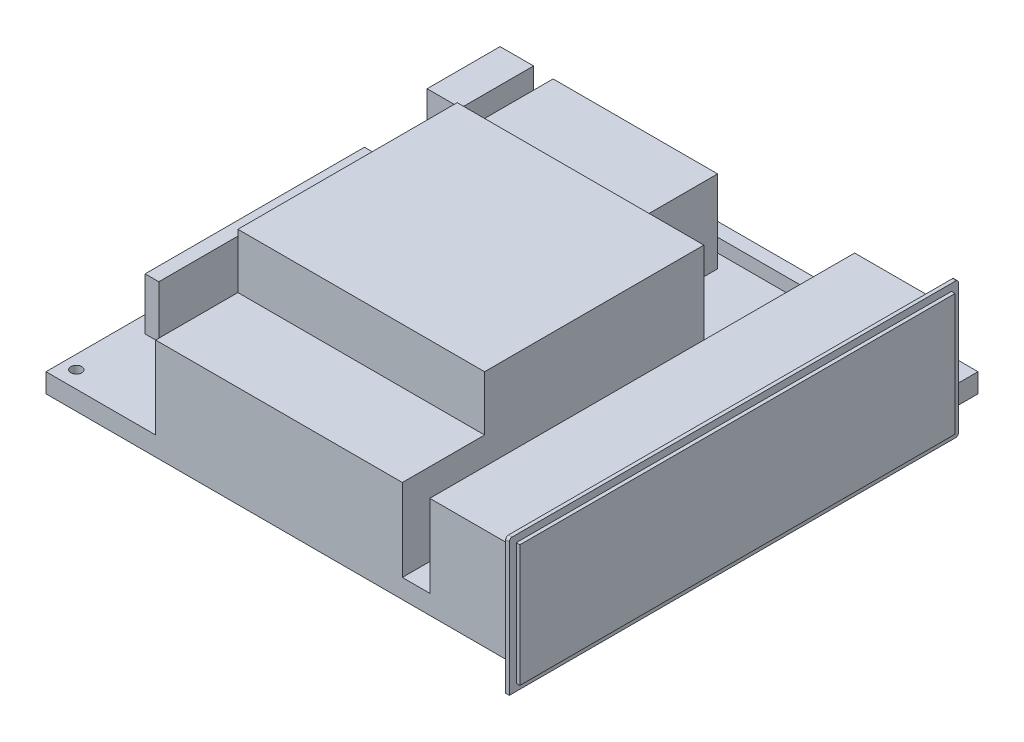
SolidWorks part; units mm, degrees
ref_plane "Front Plane" through (0, 0, 0) normal (0, 0, 1) x (1, 0, 0)
ref_plane "Top Plane" through (0, 0, 0) normal (0, 1, 0) x (1, 0, 0)
ref_plane "Right Plane" through (0, 0, 0) normal (1, 0, 0) x (0, 0, -1)
sketch "Sketch1" plane through (0, 0, 0) normal (0, 1, 0) x (1, 0, 0)
  line L1 (-85, -85) -> (85, -85)
  line L2 (-85, -85) -> (-85, 85)
  line L3 (-85, 85) -> (85, 85)
  line L4 (85, -85) -> (85, 85)
  line L5 (-85, -85) -> (85, 85) construction
  line L6 (-85, 85) -> (85, -85) construction
  point P0 (0, 0)
  dimension "D1" = 170
extrude "alusplaat" add sketch "Sketch1" along normal blind 2
sketch "Sketch2" plane through (0, 2, 0) normal (0, 1, 0) x (-1, 0, 0)
  line L1 (-85, 85) -> (-55, 85)
  line L2 (-85, 85) -> (-85, -70)
  line L3 (-85, -70) -> (-55, -70)
  line L4 (-55, 85) -> (-55, -70)
  dimension "D1" = 155
  dimension "D2" = 30
extrude "pistikud" add sketch "Sketch2" along normal blind 35
sketch "Sketch3" plane through (0, 2, 0) normal (0, 1, 0) x (1, 0, 0)
  line L0 (-85, -85) -> (55, -85) construction
  line L1 (-45, -85) -> (45, -85)
  line L2 (-45, -85) -> (-45, 25)
  line L3 (-45, 25) -> (45, 25)
  line L4 (45, -85) -> (45, 25)
  line L5 (-85, 85) -> (-85, -85) construction
  dimension "D1" = 90
  dimension "D2" = 40
  dimension "D3" = 110
extrude "cpu+mälud" add sketch "Sketch3" along normal blind 55
sketch "Sketch4" plane through (0, 2, 0) normal (0, 1, 0) x (1, 0, 0)
  line L1 (5, 35) -> (-55, 35)
  line L2 (5, 35) -> (5, 70)
  line L3 (5, 70) -> (-55, 70)
  line L4 (-55, 35) -> (-55, 70)
  line L5 (-85, 85) -> (-85, -85) construction
  line L6 (85, 85) -> (-85, 85) construction
  dimension "D1" = 35
  dimension "D2" = 60
  dimension "D3" = 30
  dimension "D4" = 15
extrude "sinine radikas" add sketch "Sketch4" along normal blind 35
sketch "Sketch5" plane through (0, 2, 0) normal (0, 1, 0) x (-1, 0, 0)
  line L0 (85, -85) -> (85, 85) construction
  line L1 (45, -75) -> (-45, -75)
  line L2 (45, -75) -> (45, -80)
  line L3 (45, -80) -> (-45, -80)
  line L4 (-45, -75) -> (-45, -80)
  line L5 (-85, -85) -> (85, -85) construction
  dimension "D1" = 90
  dimension "D2" = 40
  dimension "D3" = 5
  dimension "D4" = 5
extrude "pcie pesa" add sketch "Sketch5" along normal blind 10
sketch "Sketch6" plane through (0, 2, 0) normal (0, 1, 0) x (-1, 0, 0)
  line L1 (67.672, -48.9124) -> (79.8888, -48.9124)
  line L2 (67.672, -48.9124) -> (67.672, -75.5395)
  line L3 (67.672, -75.5395) -> (79.8888, -75.5395)
  line L4 (79.8888, -48.9124) -> (79.8888, -75.5395)
extrude "raid pesad" add sketch "Sketch6" along normal blind 30
sketch "Sketch7" plane through (0, 2, 0) normal (0, 1, 0) x (-1, 0, 0)
  line L1 (85, -85) -> (-85, -85)
  line L2 (85, -85) -> (85, 85)
  line L3 (85, 85) -> (-85, 85)
  line L4 (-85, -85) -> (-85, 85)
extrude "üleüldine müra" add sketch "Sketch7" along normal blind 5
sketch "Sketch8" plane through (0, 7, 0) normal (0, 1, 0) x (-1, 0, 0)
  line L0 (-85, -85) -> (85, -85) construction
  line L1 (78.8401, -25) -> (73.8401, -25)
  line L2 (78.8401, -25) -> (78.8401, 55)
  line L3 (78.8401, 55) -> (73.8401, 55)
  line L4 (73.8401, -25) -> (73.8401, 55)
  dimension "D1" = 5
  dimension "D2" = 80
  dimension "D3" = 60
extrude "patrei ja igasugused lülitid" add sketch "Sketch8" along normal blind 19
sketch "Sketch9" plane through (0, 57, 0) normal (0, 1, 0) x (-1, 0, 0)
  line L0 (-45, 85) -> (-45, -25) construction
  line L1 (45, -25) -> (-45, -25)
  line L2 (45, -25) -> (45, 55)
  line L3 (45, 55) -> (-45, 55)
  line L4 (-45, -25) -> (-45, 55)
  dimension "D1" = 80
extrude "mälud" cut sketch "Sketch9" against normal blind 20 flip side to cut
sketch "Sketch10" plane through (0, 7, 0) normal (0, 1, 0) x (1, 0, 0)
  line L0 (85, 85) -> (-85, 85) construction
  line L1 (74.84, 78.65) -> (-80.1, 78.65) construction
  line L2 (74.84, 78.65) -> (74.84, -78.83) construction
  line L3 (74.84, -78.83) -> (-80.1, -78.83) construction
  line L4 (-80.1, 78.65) -> (-80.1, -78.83) construction
  line L5 (85, 70) -> (85, 85) construction
  circle A0 centre (74.84, 78.65) radius 1.98
  circle A1 centre (-80.1, 78.65) radius 1.98
  circle A2 centre (-80.1, -78.83) radius 1.98
  circle A3 centre (51.98, -78.83) radius 1.98
  dimension "D6" = 3.96
  dimension "D1" = 6.35
  dimension "D2" = 10.16
  dimension "D3" = 154.94
  dimension "D4" = 157.48
  dimension "D5" = 22.86
extrude "Cut-Extrude2" cut sketch "Sketch10" against normal up to next
sketch "Sketch13" plane through (0, 7, 0) normal (0, 1, 0) x (1, 0, 0)
  line L1 (74.84, 78.65) -> (87.11, 78.65)
  line L2 (74.84, 78.65) -> (74.84, -92.9265)
  line L3 (74.84, -92.9265) -> (87.11, -92.9265)
  line L4 (87.11, 78.65) -> (87.11, -92.9265)
  dimension "D1" = 12.27
ref_plane "Plane2" through (87.11, 0, 0) normal (1, 0, 0) x (0, 0, -1)
sketch "Sketch11" plane through (87.11, 0, 0) normal (1, 0, 0) x (0, 0, -1)
  line L0 (-85, 0) -> (85, 0) construction
  line L1 (-86.875, -3.81) -> (71.875, -3.81) construction
  line L2 (-86.875, -3.81) -> (-86.875, 40.64) construction
  line L3 (-86.875, 40.64) -> (71.875, 40.64) construction
  line L4 (71.875, -3.81) -> (71.875, 40.64) construction
  line L5 (-88.415, 43.18) -> (73.415, 43.18)
  line L6 (71.875, 18.415) -> (70, 18.415) construction
  line L7 (70, 37) -> (70, 7) construction
  line L8 (-86.875, 18.415) -> (-85, 18.415) construction
  line L9 (-85, 37) -> (-85, 0) construction
  line L10 (74.415, -5.35) -> (74.415, 42.18)
  line L11 (-89.415, -6.35) -> (73.415, -6.35)
  line L12 (-89.415, -6.35) -> (-89.415, 42.18)
  line L13 (-89.415, -6.35) -> (74.415, -6.35) construction
  line L14 (74.415, -6.35) -> (74.415, 43.18) construction
  line L15 (-89.415, 43.18) -> (74.415, 43.18) construction
  line L16 (-89.415, -6.35) -> (-89.415, 43.18) construction
  arc A0 (73.415, -6.35) -> (74.415, -5.35) centre (73.415, -5.35) ccw
  arc A1 (74.415, 42.18) -> (73.415, 43.18) centre (73.415, 42.18) ccw
  arc A2 (-88.415, 43.18) -> (-89.415, 42.18) centre (-88.415, 42.18) ccw
  dimension "D5" = 1
  dimension "D1" = 158.75
  dimension "D2" = 44.45
  dimension "D3" = 3.81
  dimension "D4" = 2.54
extrude "Boss-Extrude1" add sketch "Sketch11" along normal blind 1.32
sketch "Sketch12" plane through (88.43, 0, 0) normal (1, 0, 0) x (0, 0, -1)
  line L1 (-86.875, -3.81) -> (71.875, -3.81)
  line L2 (-86.875, -3.81) -> (-86.875, 40.64)
  line L3 (-86.875, 40.64) -> (71.875, 40.64)
  line L4 (71.875, -3.81) -> (71.875, 40.64)
  line L5 (-88.415, 43.18) -> (73.415, 43.18)
  line L10 (74.415, -5.35) -> (74.415, 42.18)
  line L11 (-89.415, -6.35) -> (73.415, -6.35)
  line L12 (-89.415, -6.35) -> (-89.415, 42.18)
  line L13 (-89.415, -6.35) -> (74.415, -6.35) construction
  line L14 (74.415, -6.35) -> (74.415, 43.18) construction
  line L15 (-89.415, 43.18) -> (74.415, 43.18) construction
  line L16 (-89.415, -6.35) -> (-89.415, 43.18) construction
  arc A0 (73.415, -6.35) -> (74.415, -5.35) centre (73.415, -5.35) ccw
  arc A1 (74.415, 42.18) -> (73.415, 43.18) centre (73.415, 42.18) ccw
  arc A2 (-88.415, 43.18) -> (-89.415, 42.18) centre (-88.415, 42.18) ccw
  arc A5 (-88.415, 43.18) -> (-89.415, 42.18) centre (-88.415, 42.18) ccw construction
  dimension "D5" = 1
  dimension "D1" = 158.75
  dimension "D2" = 44.45
  dimension "D4" = 2.54
extrude "Boss-Extrude2" add sketch "Sketch12" along normal blind 1.32 contours L1 L4 L3 L2 region at (88.43, 18.415, 7.5)
